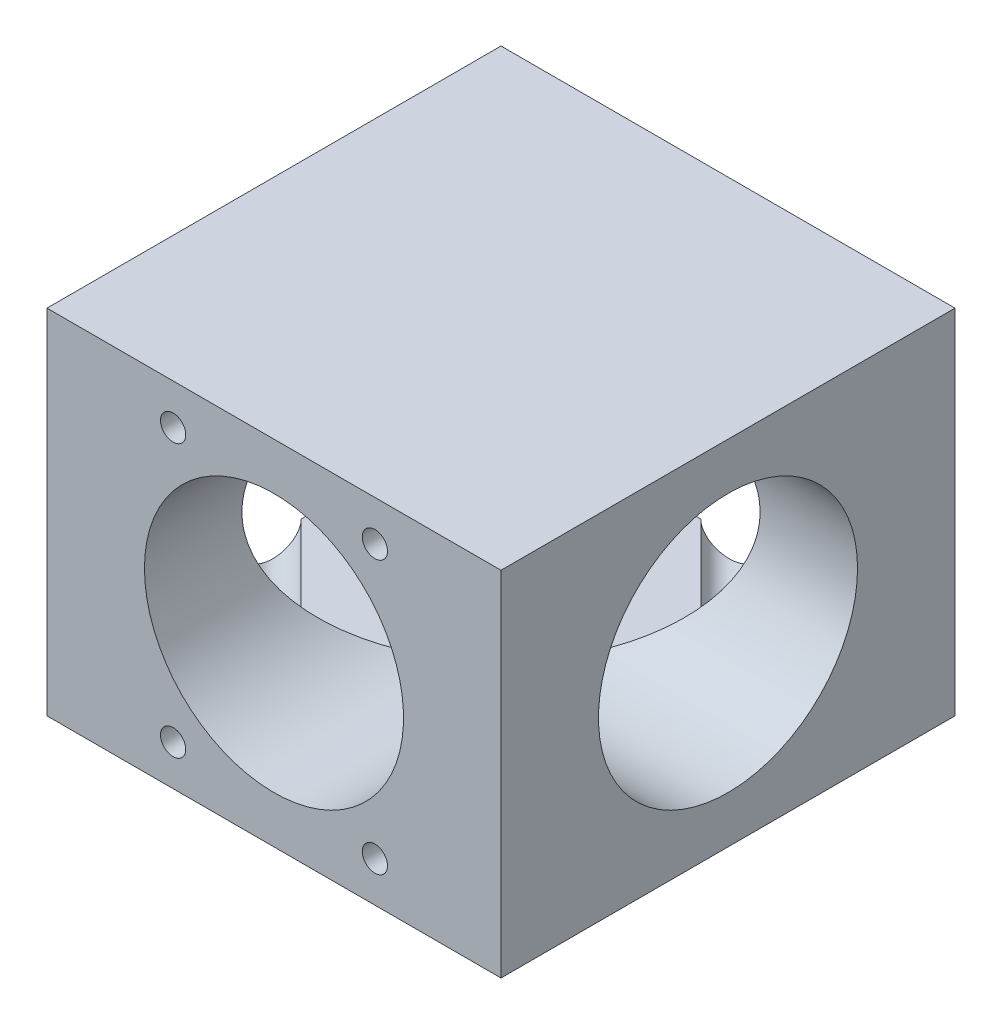
SolidWorks part; units mm, degrees
material "7075-T6 (SN)"
ref_plane "Front Plane" through (0, 0, 0) normal (0, 0, 1) x (1, 0, 0)
ref_plane "Top Plane" through (0, 0, 0) normal (0, 1, 0) x (1, 0, 0)
ref_plane "Right Plane" through (0, 0, 0) normal (1, 0, 0) x (0, 0, -1)
sketch "Sketch1" plane through (0, 0, 0) normal (0, 1, 0) x (1, 0, 0)
  line L1 (-22.5, -22.5) -> (22.5, -22.5)
  line L2 (-22.5, -22.5) -> (-22.5, 22.5)
  line L3 (-22.5, 22.5) -> (22.5, 22.5)
  line L4 (22.5, -22.5) -> (22.5, 22.5)
  line L5 (-22.5, -22.5) -> (22.5, 22.5) construction
  line L6 (-22.5, 22.5) -> (22.5, -22.5) construction
  point P0 (0, 0)
  dimension "D1" = 45
extrude "Boss-Extrude1" add sketch "Sketch1" along normal mid plane 35
sketch "Sketch2" plane through (22.5, 0, 0) normal (1, 0, 0) x (0, 0, -1)
  circle A0 centre (0, 0) radius 12.8397
  dimension "D1" = 25.6794
extrude "Cut-Extrude1" cut sketch "Sketch2" against normal up to next
sketch "Sketch3" plane through (0, 0, -22.5) normal (0, 0, -1) x (-1, 0, 0)
  circle A0 centre (0, 0) radius 12.8397
  dimension "D1" = 25.6794
extrude "Cut-Extrude2" cut sketch "Sketch3" against normal through all
sketch "Sketch5" plane through (0, 0, 0) normal (0, 1, 0) x (1, 0, 0)
  line L0 (-12.7279, -12.7279) -> (12.7279, 12.7279)
  line L1 (12.7279, 12.7279) -> (11.9147, 13.5411)
  line L2 (11.9147, 13.5411) -> (-13.5411, -11.9147)
  line L3 (-13.5411, -11.9147) -> (-12.7279, -12.7279)
  line L4 (22.5, -22.5) -> (22.5, 22.5) construction
  dimension "D1" = 45
  dimension "D2" = 1.15
  dimension "D3" = 36
extrude "Cut-Extrude3" cut sketch "Sketch5" against normal mid plane 26.4
sketch "Sketch7" plane through (0, 0, 0) normal (-0.7071, 0, -0.7071) x (-0.7071, 0, 0.7071)
  line L0 (-16, 13.2) -> (-16, -13.2) construction
  line L1 (-18, 13.2) -> (18, 13.2)
  line L2 (-18, 13.2) -> (-18, -13.2)
  line L3 (-18, -13.2) -> (18, -13.2)
  line L4 (18, 13.2) -> (18, -13.2)
  line L8 (-14, 13.2) -> (-14, -13.2)
  line L11 (-18, 13.2) -> (-18, -13.2)
  line L12 (16, 13.2) -> (16, -13.2) construction
  line L15 (18, 13.2) -> (18, -13.2)
  line L19 (14, 13.2) -> (14, -13.2)
  arc A4 (-14, 13.2) -> (-18, 13.2) centre (-16, 13.2) ccw
  arc A5 (-18, -13.2) -> (-14, -13.2) centre (-16, -13.2) ccw
  arc A10 (18, 13.2) -> (14, 13.2) centre (16, 13.2) ccw
  arc A11 (14, -13.2) -> (18, -13.2) centre (16, -13.2) ccw
  point P7 (-16, 0)
  point P15 (16, 0)
  dimension "D2" = 2
extrude "Cut-Extrude4" cut sketch "Sketch7" along normal up to vertex (31.8198 mm away) contours L11 A5 L8 A4 | L2 L1 L4 L3 | L19 A11 L15 A10 up to point (-22.5, -17.5, -22.5)
hole_wizard "M3 Tapped Hole1" positions "Sketch9" profile "Sketch10" tap size "M3" standard "DIN"
sketch "Sketch9" plane through (0, 0, 22.5) normal (0, 0, 1) x (1, 0, 0)
  line L0 (-22.5, -17.5) -> (22.5, -17.5) construction
  line L1 (-22.5, 17.5) -> (22.5, 17.5) construction
  point P0 (-10, -13.5)
  point P2 (10, -13.5)
  point P4 (10, 13.5)
  point P6 (-10, 13.5)
  dimension "D1" = 4
  dimension "D2" = 4
  dimension "D3" = 10
  dimension "D4" = 10
sketch "Sketch10" plane through (-10, -13.5, 22.5) normal (1, 0, 0) x (0, -1, 0)
  line L0 (0, 0) -> (0, 7.2511)
  line L1 (0, 7.2511) -> (1.25, 6.5)
  line L2 (1.25, 6.5) -> (1.25, 0)
  line L5 (1.25, 0) -> (0, 0)
  line L10 (0, 7.2511) -> (-1.25, 6.5) construction
  line L11 (0, -6.35) -> (0, 107.95) construction
  dimension "Tap Drill Dia." = 2.5
  dimension "Tap Drill Depth" = 6.5
  dimension "Drill Angle" = 118
cosmetic thread "Hole Thread1" parameters "D1"=5, "D2"=3
cosmetic thread "Hole Thread2" parameters "D1"=5, "D2"=3
cosmetic thread "Hole Thread3" parameters "D1"=5, "D2"=3
cosmetic thread "Hole Thread4" parameters "D1"=5, "D2"=3
hole_wizard "M3 Tapped Hole2" positions "Sketch11" profile "Sketch12" tap size "M3" standard "DIN"
sketch "Sketch11" plane through (0, 0, -22.5) normal (0, 0, -1) x (-1, 0, 0)
  circle A0 centre (-10, 13.5) radius 1.25 construction
  circle A1 centre (-10, -13.5) radius 1.25 construction
  point P0 (-10, 13.5)
  point P2 (-10, -13.5)
sketch "Sketch12" plane through (10, 13.5, -22.5) normal (1, 0, 0) x (0, 1, 0)
  line L0 (0, 0) -> (0, 6.2511)
  line L1 (0, 6.2511) -> (1.25, 5.5)
  line L2 (1.25, 5.5) -> (1.25, 0)
  line L5 (1.25, 0) -> (0, 0)
  line L10 (0, 6.2511) -> (-1.25, 5.5) construction
  line L11 (0, -6.35) -> (0, 107.95) construction
  dimension "Tap Drill Dia." = 2.5
  dimension "Tap Drill Depth" = 5.5
  dimension "Drill Angle" = 118
cosmetic thread "Hole Thread5" parameters "D1"=4, "D2"=3
cosmetic thread "Hole Thread6" parameters "D1"=4, "D2"=3
hole_wizard "M2 Tapped Hole1" positions "Sketch15" profile "Sketch16" tap size "M2" standard "DIN"
sketch "Sketch15" plane through (0, 0, 0) normal (-0.7071, 0, -0.7071) x (-0.7071, 0, 0.7071)
  point P0 (-16, -13.75)
  point P2 (-16, 13.75)
  point P4 (16, 13.75)
  point P6 (16, -13.75)
  point P9 (0, 0)
  point P10 (0, 0)
  point P11 (0, 0)
  point P16 (0, -14.2517)
  dimension "D1" = 27.5
  dimension "D2" = 32
  dimension "D3" = 16
  dimension "D4" = 13.75
sketch "Sketch16" plane through (11.3137, -13.75, -11.3137) normal (0, 1, 0) x (-0.7071, 0, 0.7071)
  line L0 (0, 0) -> (0, 5.6807)
  line L1 (0, 5.6807) -> (0.8, 5.2)
  line L2 (0.8, 5.2) -> (0.8, 0)
  line L5 (0.8, 0) -> (0, 0)
  line L10 (0, 5.6807) -> (-0.8, 5.2) construction
  line L11 (0, -6.35) -> (0, 107.95) construction
  dimension "Tap Drill Dia." = 1.6
  dimension "Tap Drill Depth" = 5.2
  dimension "Drill Angle" = 118
cosmetic thread "Hole Thread7" parameters "D1"=4, "D2"=2
cosmetic thread "Hole Thread8" parameters "D1"=4, "D2"=2
cosmetic thread "Hole Thread9" parameters "D1"=4, "D2"=2
cosmetic thread "Hole Thread10" parameters "D1"=4, "D2"=2
